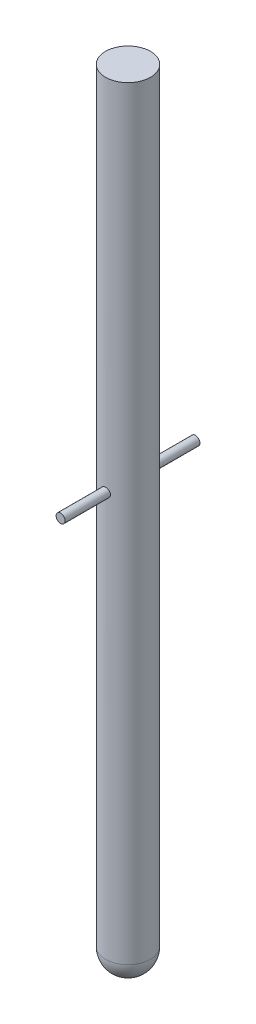
SolidWorks part; units mm, degrees
material "Guma"
ref_plane "Płaszczyzna przednia" through (0, 0, 0) normal (0, 0, 1) x (1, 0, 0)
ref_plane "Płaszczyzna górna" through (0, 0, 0) normal (0, 1, 0) x (1, 0, 0)
ref_plane "Płaszczyzna prawa" through (0, 0, 0) normal (1, 0, 0) x (0, 0, -1)
sketch "Szkic2" plane through (0, 0, 0) normal (0, 1, 0) x (1, 0, 0)
  circle A0 centre (0, 0) radius 5
extrude "Dodanie-wyciągnięcie1" add sketch "Szkic2" along normal blind 175
sketch "Szkic3" plane through (0, 0, 0) normal (0, 0, 1) x (1, 0, 0)
  circle A0 centre (0, 95) radius 1
extrude "Dodanie-wyciągnięcie2" add sketch "Szkic3" along normal blind 15 and the other way blind 15
fillet "Zaokrąglenie1" radius 5 1 edges at (0, 0, 5)
